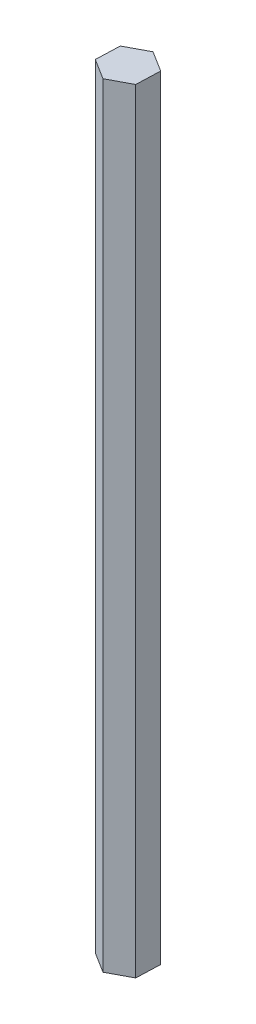
SolidWorks part; units mm, degrees
ref_plane "Спереди" through (0, 0, 0) normal (0, 0, 1) x (1, 0, 0)
ref_plane "Сверху" through (0, 0, 0) normal (0, 1, 0) x (1, 0, 0)
ref_plane "Справа" through (0, 0, 0) normal (1, 0, 0) x (0, 0, -1)
sketch "Эскиз1" plane through (0, 0, 0) normal (0, 1, 0) x (1, 0, 0)
  line L1 (3.179, -1.9891) -> (3.3121, 1.7585)
  line L2 (3.3121, 1.7585) -> (0.1331, 3.7476)
  line L3 (0.1331, 3.7476) -> (-3.179, 1.9891)
  line L4 (-3.179, 1.9891) -> (-3.3121, -1.7585)
  line L5 (-3.3121, -1.7585) -> (-0.1331, -3.7476)
  line L6 (-0.1331, -3.7476) -> (3.179, -1.9891)
  circle A0 centre (0, 0) radius 3.75 construction
extrude "Бобышка-Вытянуть1" add sketch "Эскиз1" along normal blind 120
